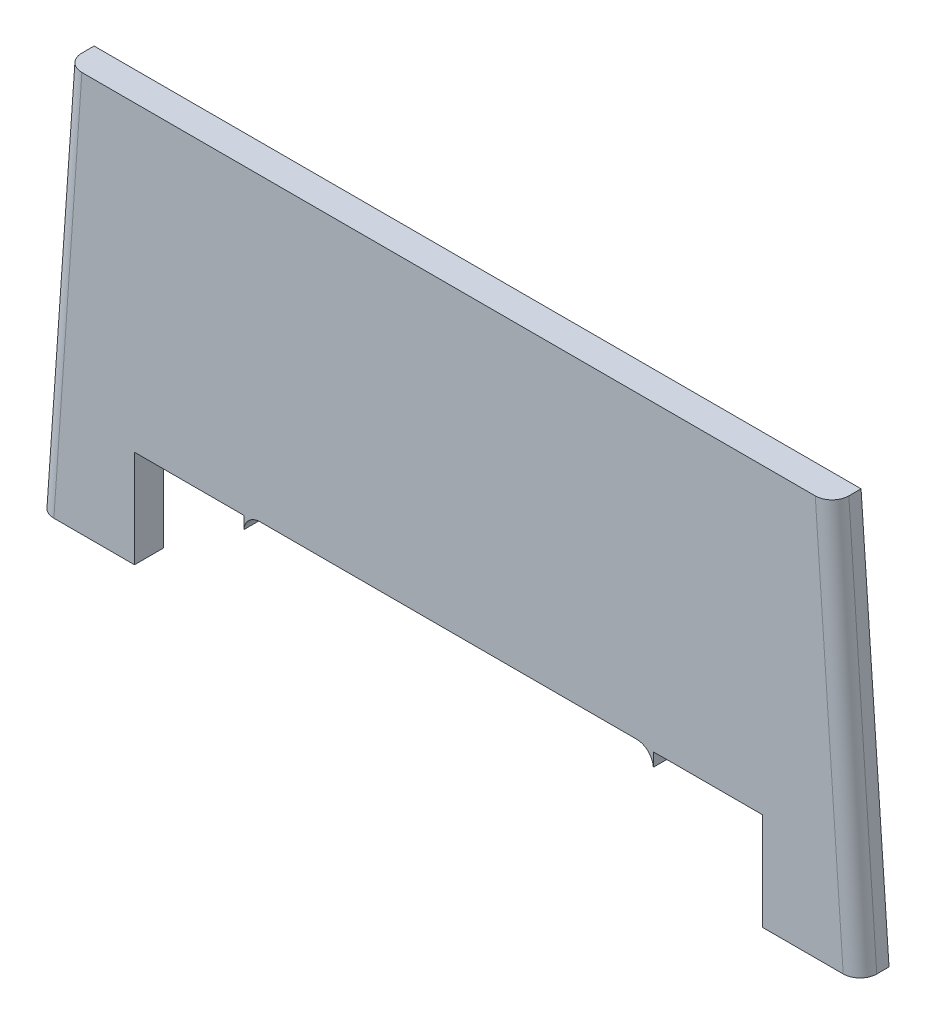
SolidWorks part; units mm, degrees
ref_plane "Front Plane" through (0, 0, 0) normal (0, 0, 1) x (1, 0, 0)
ref_plane "Top Plane" through (0, 0, 0) normal (0, 1, 0) x (1, 0, 0)
ref_plane "Right Plane" through (0, 0, 0) normal (1, 0, 0) x (0, 0, -1)
sketch "Sketch1" plane through (0, 0, 577.2661) normal (0, 0, -1) x (-1, 0, 0)
  line L0 (246.3735, 767.5882) -> (232.8406, 767.5882) construction
  line L1 (221.3735, 767.5882) -> (232.8406, 767.5882) construction
  line L2 (221.3735, 767.5882) -> (-342.0733, 767.5882) construction
  line L3 (-342.0733, 767.5882) -> (-353.5403, 767.5882) construction
  line L4 (-353.5403, 767.5882) -> (-367.0733, 767.5882) construction
  line L5 (-389.4499, 447.5882) -> (-367.0733, 767.5882) construction
  line L6 (-375.9499, 447.5882) -> (-389.4499, 447.5882) construction
  line L8 (-311.5499, 447.5882) -> (-364.4499, 447.5882) construction
  line L9 (-311.5499, 525.5882) -> (-311.5499, 447.5882) construction
  line L10 (-224.1065, 525.5004) -> (-239.4907, 525.5882) construction
  line L11 (-239.4907, 525.5882) -> (-311.4907, 525.5882) construction
  line L12 (268.7501, 447.5882) -> (255.2501, 447.5882) construction
  line L13 (255.2172, 447.5882) -> (243.7501, 447.5882) construction
  line L14 (190.8501, 447.5882) -> (243.7501, 447.5882) construction
  line L15 (190.8501, 525.5882) -> (190.8501, 447.5882) construction
  line L16 (103.4501, 525.5882) -> (190.8501, 525.5882) construction
  line L17 (103.4068, 514.7948) -> (103.4068, 525.5004) construction
  line L19 (-224.1065, 514.7948) -> (-224.1065, 525.5004) construction
  line L20 (246.3735, 767.5882) -> (232.8406, 767.5882)
  line L21 (221.3735, 767.5882) -> (232.8406, 767.5882)
  line L22 (221.3735, 767.5882) -> (-342.0733, 767.5882)
  line L23 (-342.0733, 767.5882) -> (-353.5403, 767.5882)
  line L24 (-353.5403, 767.5882) -> (-367.0733, 767.5882)
  line L25 (-389.4499, 447.5882) -> (-367.0733, 767.5882)
  line L26 (-375.9499, 447.5882) -> (-389.4499, 447.5882)
  line L27 (-375.9499, 447.5882) -> (-364.4499, 447.5882)
  line L28 (-311.5499, 447.5882) -> (-364.4499, 447.5882)
  line L29 (-311.5499, 525.5882) -> (-311.5499, 447.5882)
  line L30 (-224.1065, 525.5004) -> (-239.4907, 525.5882)
  line L31 (-239.4907, 525.5882) -> (-311.4907, 525.5882)
  line L32 (268.7501, 447.5882) -> (255.2501, 447.5882)
  line L33 (255.2172, 447.5882) -> (243.7501, 447.5882)
  line L34 (190.8501, 447.5882) -> (243.7501, 447.5882)
  line L35 (190.8501, 525.5882) -> (190.8501, 447.5882)
  line L36 (103.4501, 525.5882) -> (190.8501, 525.5882)
  line L37 (103.4068, 515.649) -> (103.4068, 525.5004)
  line L38 (-210.625, 527.5882) -> (90.4501, 527.5882)
  line L39 (-224.1065, 514.7948) -> (-224.1065, 525.5004)
  line L40 (268.7501, 447.5882) -> (246.3735, 767.5882)
  line L41 (-311.4907, 525.5882) -> (-311.5499, 525.5882)
  line L42 (255.2501, 447.5882) -> (255.2172, 447.5882)
  line L43 (103.4068, 525.5004) -> (103.4501, 525.5882)
  arc A0 (103.4501, 514.5882) -> (90.4501, 527.5882) centre (90.4501, 514.5882) ccw construction
  arc A1 (-210.625, 527.5882) -> (-224.1065, 514.7948) centre (-210.625, 514.0882) ccw construction
  arc A2 (103.4068, 515.649) -> (90.4501, 527.5882) centre (90.4501, 514.5882) ccw
  arc A3 (-210.625, 527.5882) -> (-224.1065, 514.7948) centre (-210.625, 514.0882) ccw
extrude "Boss-Extrude1" add sketch "Sketch1" along normal blind 23.2
fillet "Fillet1" radius 13.4 2 edges at (378.2616, 607.5882, 577.2661) (-257.5618, 607.5882, 577.2661)
shell "Shell1" thickness 1 removed face at (61.2897, 535.6076, 554.0661)
sketch "Sketch2" plane through (0, 0, 554.0661) normal (0, 0, -1) x (-1, 0, 0)
  line L0 (246.3735, 767.5882) -> (-367.0733, 767.5882) construction
  line L1 (268.7501, 447.5882) -> (246.3735, 767.5882) construction
  line L2 (190.8501, 447.5882) -> (268.7501, 447.5882) construction
  line L3 (190.8501, 525.1765) -> (190.8501, 447.5882) construction
  line L4 (103.4501, 525.5882) -> (190.6124, 525.5882) construction
  line L5 (103.4068, 515.649) -> (103.4068, 525.5004) construction
  line L6 (-210.625, 527.5882) -> (90.4501, 527.5882) construction
  line L7 (-224.1065, 525.5004) -> (-224.1065, 514.7948) construction
  line L8 (-239.4907, 525.5882) -> (-224.1065, 525.5004) construction
  line L9 (-311.3122, 525.5882) -> (-239.4907, 525.5882) construction
  line L10 (-311.5499, 447.5882) -> (-311.5499, 525.5882) construction
  line L11 (-367.0733, 767.5882) -> (-389.4499, 447.5882) construction
  line L12 (-389.4499, 447.5882) -> (-311.5499, 447.5882) construction
  line L13 (246.3735, 767.5882) -> (-367.0733, 767.5882)
  line L14 (268.7501, 447.5882) -> (246.3735, 767.5882)
  line L15 (190.8501, 447.5882) -> (268.7501, 447.5882)
  line L16 (190.8501, 525.1765) -> (190.8501, 447.5882)
  line L17 (103.4501, 525.5882) -> (190.6124, 525.5882)
  line L18 (103.4068, 515.649) -> (103.4068, 525.5004)
  line L19 (-210.625, 527.5882) -> (90.4501, 527.5882)
  line L20 (-224.1065, 525.5004) -> (-224.1065, 514.7948)
  line L21 (-239.4907, 525.5882) -> (-224.1065, 525.5004)
  line L22 (-311.3122, 525.5882) -> (-239.4907, 525.5882)
  line L23 (-311.5499, 447.5882) -> (-311.5499, 525.5882)
  line L24 (-367.0733, 767.5882) -> (-389.4499, 447.5882)
  line L25 (-389.4499, 447.5882) -> (-311.5499, 447.5882)
  line L26 (103.4501, 525.5882) -> (103.4068, 525.5004)
  line L27 (-311.5499, 525.5882) -> (-311.3122, 525.5882)
  line L28 (190.6124, 525.5882) -> (190.8501, 525.5882)
  line L29 (190.8501, 525.5882) -> (190.8501, 525.1765)
  arc A0 (103.4068, 515.649) -> (90.4501, 527.5882) centre (90.4501, 514.5882) ccw construction
  arc A1 (-210.625, 527.5882) -> (-224.1065, 514.7948) centre (-210.625, 514.0882) ccw construction
  arc A2 (103.4068, 515.649) -> (90.4501, 527.5882) centre (90.4501, 514.5882) ccw
  arc A3 (-210.625, 527.5882) -> (-224.1065, 514.7948) centre (-210.625, 514.0882) ccw
extrude "Boss-Extrude2" add sketch "Sketch2" against normal blind 0.6
